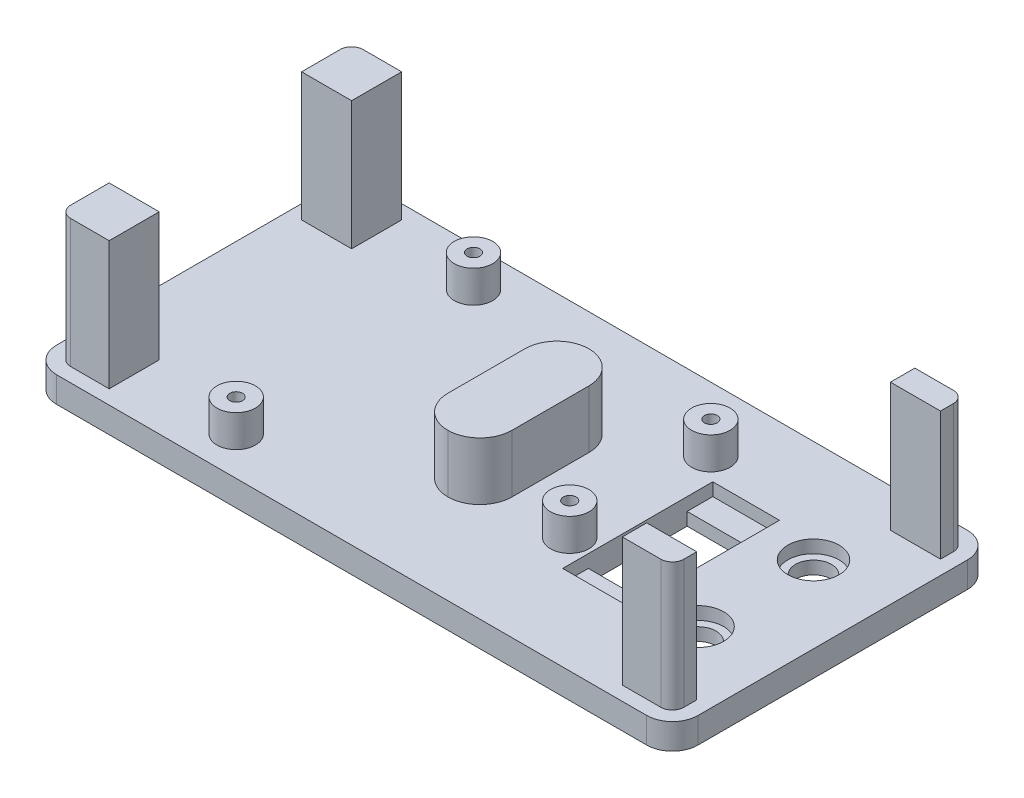
SolidWorks part; units mm, degrees
ref_plane "Front Plane" through (0, 0, 0) normal (0, 0, 1) x (1, 0, 0)
ref_plane "Top Plane" through (0, 0, 0) normal (0, 1, 0) x (1, 0, 0)
ref_plane "Right Plane" through (0, 0, 0) normal (1, 0, 0) x (0, 0, -1)
sketch "Sketch1" plane through (0, 0, 0) normal (0, 1, 0) x (1, 0, 0)
  line L1 (0, 0) -> (127, 0)
  line L2 (0, 0) -> (0, 63.5)
  line L3 (0, 63.5) -> (127, 63.5)
  line L4 (127, 0) -> (127, 63.5)
  dimension "D1" = 127
  dimension "D2" = 63.5
extrude "Boss-Extrude1" add sketch "Sketch1" along normal blind 5.08
sketch "Sketch2" plane through (0, 5.08, 0) normal (0, 1, 0) x (1, 0, 0)
  line L0 (63.5, 63.5) -> (63.5, 0) construction
  line L1 (127, 63.5) -> (0, 63.5) construction
  line L2 (0, 0) -> (127, 0) construction
  line L3 (0, 31.75) -> (127, 31.75) construction
  line L4 (0, 63.5) -> (0, 0) construction
  line L5 (127, 0) -> (127, 63.5) construction
  line L6 (12.7, 2.794) -> (12.7, 12.7)
  line L7 (2.794, 60.706) -> (12.7, 60.706)
  line L8 (2.794, 60.706) -> (2.794, 50.8)
  line L9 (2.794, 50.8) -> (12.7, 50.8)
  line L10 (12.7, 60.706) -> (12.7, 50.8)
  line L11 (2.794, 12.7) -> (12.7, 12.7)
  line L12 (2.794, 2.794) -> (2.794, 12.7)
  line L13 (2.794, 2.794) -> (12.7, 2.794)
  line L14 (124.206, 2.794) -> (124.206, 7.62)
  line L15 (114.3, 60.706) -> (124.206, 60.706)
  line L16 (114.3, 60.706) -> (114.3, 55.88)
  line L17 (114.3, 55.88) -> (124.206, 55.88)
  line L18 (124.206, 60.706) -> (124.206, 55.88)
  line L19 (114.3, 7.62) -> (124.206, 7.62)
  line L20 (114.3, 2.794) -> (114.3, 7.62)
  line L21 (114.3, 2.794) -> (124.206, 2.794)
  dimension "D1" = 9.906
  dimension "D2" = 9.906
  dimension "D3" = 2.794
  dimension "D4" = 2.794
  dimension "D5" = 2.794
  dimension "D6" = 2.794
  dimension "D7" = 4.826
  dimension "D8" = 9.906
extrude "Boss-Extrude3" add sketch "Sketch2" along normal blind 25.4
fillet "Fillet3" radius 2.286 4 edges at (124.206, 17.78, -60.706) (124.206, 17.78, -2.794) (2.794, 17.78, -2.794) (2.794, 17.78, -60.706)
fillet "Fillet4" radius 5.08 4 edges at (0, 2.54, -63.5) (127, 2.54, -63.5) (127, 2.54, 0) (0, 2.54, 0)
sketch "Sketch4" plane through (0, 5.08, 0) normal (0, 1, 0) x (1, 0, 0)
  circle A0 centre (31.75, 55.88) radius 3.81
  circle A1 centre (33.02, 7.62) radius 3.81
  circle A2 centre (83.82, 50.8) radius 3.81
  circle A3 centre (83.82, 22.86) radius 3.81
  dimension "D1" = 7.62
  dimension "D2" = 7.62
  dimension "D7" = 52.07
  dimension "D11" = 7.62
  dimension "D12" = 7.62
  dimension "D3" = 15.24
  dimension "D4" = 19.05
  dimension "D5" = 48.26
  dimension "D6" = 7.62
  dimension "D9" = 27.94
  dimension "D10" = 50.8
sketch "Sketch7" plane through (0, 5.08, 0) normal (0, 1, 0) x (1, 0, 0)
  line L0 (121.92, 63.5) -> (5.08, 63.5) construction
  line L1 (58.42, 45.72) -> (71.12, 45.72)
  line L2 (58.42, 45.72) -> (58.42, 17.78)
  line L3 (58.42, 17.78) -> (71.12, 17.78)
  line L4 (71.12, 45.72) -> (71.12, 17.78)
  dimension "D1" = 12.7
  dimension "D2" = 17.78
  dimension "D3" = 17.78
  dimension "D4" = 53.34
sketch "Sketch13" plane through (0, 5.08, 0) normal (0, 1, 0) x (1, 0, 0)
  line L0 (121.92, 63.5) -> (5.08, 63.5) construction
  line L1 (5.08, 0) -> (121.92, 0) construction
  line L2 (127, 5.08) -> (127, 58.42) construction
  line L4 (88.392, 41.529) -> (101.6, 41.529)
  line L5 (88.392, 41.529) -> (88.392, 21.971)
  line L6 (88.392, 21.971) -> (101.6, 21.971)
  line L7 (101.6, 41.529) -> (101.6, 21.971)
  circle A0 centre (111.76, 43.18) radius 3.556
  circle A1 centre (111.76, 20.32) radius 3.556
  dimension "D1" = 7.112
  dimension "D2" = 7.112
  dimension "D3" = 20.32
  dimension "D4" = 20.32
  dimension "D5" = 15.24
  dimension "D6" = 19.558
  dimension "D7" = 13.208
  dimension "D8" = 25.4
  dimension "D9" = 16.891
extrude "Cut-Extrude8" cut sketch "Sketch13" against normal up to next
sketch "Sketch14" plane through (0, 5.08, 0) normal (0, 1, 0) x (1, 0, 0)
  line L0 (88.392, 41.529) -> (88.392, 21.971) construction
  line L1 (88.392, 46.609) -> (101.6, 46.609)
  line L2 (88.392, 46.609) -> (88.392, 16.891)
  line L3 (88.392, 16.891) -> (101.6, 16.891)
  line L4 (101.6, 46.609) -> (101.6, 16.891)
  line L5 (101.6, 21.971) -> (101.6, 41.529) construction
  dimension "D1" = 5.08
  dimension "D2" = 5.08
extrude "Cut-Extrude9" cut sketch "Sketch14" against normal blind 2.54
extrude "Boss-Extrude10" add sketch "Sketch4" along normal blind 6.35
extrude "Boss-Extrude11" add sketch "Sketch7" along normal blind 11.43
sketch "Sketch18" plane through (0, 11.43, 0) normal (0, 1, 0) x (1, 0, 0)
  circle A0 centre (31.75, 55.88) radius 1.27
  circle A1 centre (83.82, 50.8) radius 1.27
  circle A2 centre (83.82, 22.86) radius 1.27
  circle A3 centre (33.02, 7.62) radius 1.27
  dimension "D1" = 2.54
  dimension "D2" = 2.54
  dimension "D3" = 2.54
  dimension "D4" = 2.54
extrude "Cut-Extrude11" cut sketch "Sketch18" against normal blind 8.89
fillet "Fillet6" radius 6.35 4 edges at (71.12, 10.795, -45.72) (58.42, 10.795, -45.72) (71.12, 10.795, -17.78) (58.42, 10.795, -17.78)
sketch "Sketch19" plane through (0, 5.08, 0) normal (0, 1, 0) x (1, 0, 0)
  circle A0 centre (111.76, 43.18) radius 5.08
  circle A1 centre (111.76, 20.32) radius 5.08
  dimension "D1" = 10.16
  dimension "D2" = 10.16
extrude "Cut-Extrude12" cut sketch "Sketch19" against normal blind 2.54
